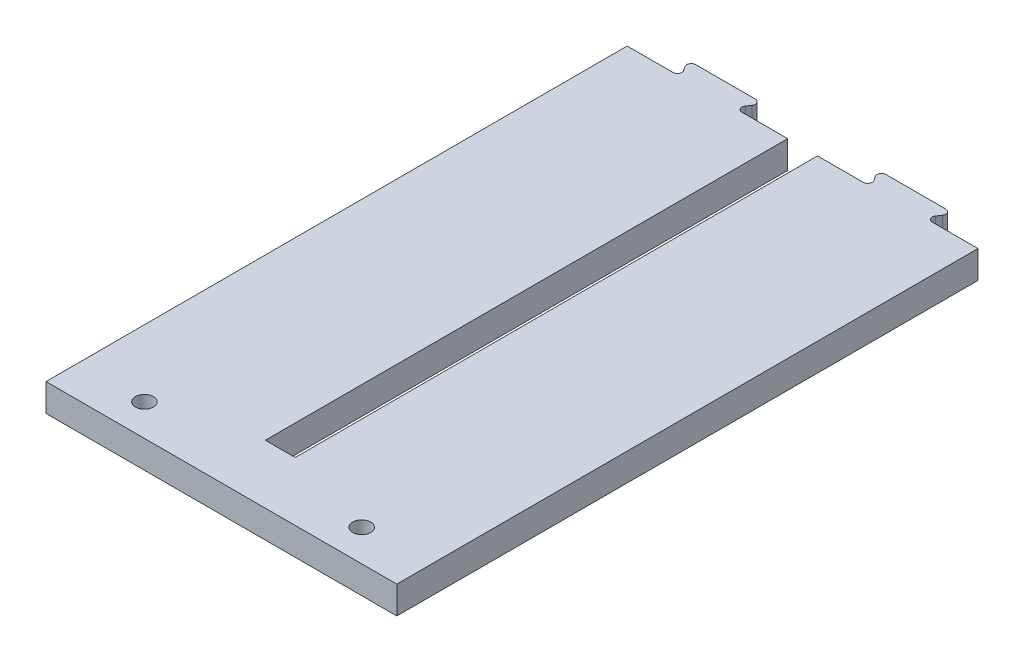
SolidWorks part; units mm, degrees
ref_plane "Front Plane" through (0, 0, 0) normal (0, 0, 1) x (1, 0, 0)
ref_plane "Top Plane" through (0, 0, 0) normal (0, 1, 0) x (1, 0, 0)
ref_plane "Right Plane" through (0, 0, 0) normal (1, 0, 0) x (0, 0, -1)
sketch "Sketch1" plane through (0, 0, 0) normal (0, 1, 0) x (1, 0, 0)
  line L1 (-19.375, 0) -> (19.375, 0)
  line L2 (-19.375, 0) -> (-19.375, 72.5)
  line L3 (-19.375, 72.5) -> (19.375, 72.5)
  line L4 (19.375, 0) -> (19.375, 72.5)
  point P5 (0, 0)
  dimension "D1" = 38.75
  dimension "D2" = 72.5
extrude "Boss-Extrude1" add sketch "Sketch1" along normal blind 3.05 contours L2 | L1 L4 L3 L2 | L4 region at (0, 0, -36.25)
sketch "Sketch4" plane through (0, 3.05, 0) normal (0, 1, 0) x (1, 0, 0)
  line L0 (-19.375, 72.5) -> (19.375, 72.5) construction
  line L2 (-19.375, 0) -> (19.375, 0) construction
  line L3 (1.65, 70.5) -> (-1.65, 70.5)
  line L4 (-1.65, 70.5) -> (-1.65, 69.5)
  line L5 (-1.65, 69.5) -> (1.65, 69.5)
  line L6 (1.65, 69.5) -> (1.65, 70.5)
  line L7 (0, 0) -> (0, 72.5) construction
  line L9 (1.65, 68.3) -> (-1.65, 68.3)
  line L10 (-1.65, 68.3) -> (-1.65, 6.5)
  line L11 (-1.65, 6.5) -> (1.65, 6.5)
  line L12 (1.65, 6.5) -> (1.65, 68.3)
  point P6 (0, 6.5)
  point P10 (0, 70.5)
  point P22 (0, 68.3)
  dimension "D1" = 2
  dimension "D2" = 1
  dimension "D3" = 1.2
  dimension "D4" = 3.3
  dimension "D7" = 6.5
extrude "Cut-Extrude1" cut sketch "Sketch4" against normal through all contours L5 L7 L3 L4 | L11 L7 L9 L10 | L7 L11 L12 L9 | L7 L5 L6 L3 | L6 L3 L4 L5 region at (0.825, 3.05, -70) region at (0.825, 3.05, -37.4) region at (-0.825, 3.05, -37.4) region at (-0.825, 3.05, -70)
sketch "Sketch7" plane through (0, 3.05, 0) normal (0, 1, 0) x (1, 0, 0)
  line L0 (0, 0) -> (-12, 0)
  line L1 (-19.375, 0) -> (19.375, 0) construction
  line L2 (-12, 0) -> (-12, 3.5)
  line L4 (0, 0) -> (0, 70) construction
  circle A0 centre (-12, 3.5) radius 1
  circle A2 centre (12, 3.5) radius 1
  dimension "D3" = 2
  dimension "D1" = 12
  dimension "D2" = 3.5
extrude "Cut-Extrude4" cut sketch "Sketch7" against normal through all contours A0 L2 | L2 A0 | A2 region at (-11.3129, 3.05, -2.8129)
sketch "Sketch8" plane through (0, 3.05, 0) normal (0, 1, 0) x (1, 0, 0)
  line L0 (19.375, 0) -> (19.375, 72.5) construction
  line L1 (-19.375, 72.5) -> (19.375, 72.5)
  line L2 (-19.375, 72.5) -> (-19.375, 64.2)
  line L3 (-19.375, 64.2) -> (19.375, 64.2)
  line L4 (19.375, 72.5) -> (19.375, 64.2)
  dimension "D1" = 8.3
extrude "Cut-Extrude5" cut sketch "Sketch8" against normal through all
sketch "Sketch9" plane through (0, 3.05, 0) normal (0, 1, 0) x (1, 0, 0)
  line L0 (-19.375, 64.2) -> (19.375, 64.2) construction
  line L1 (-19.375, 64.2) -> (-19.375, 66.2) construction
  line L2 (19.375, 64.2) -> (19.375, 66.2) construction
  line L3 (-19.375, 66.2) -> (19.375, 66.2) construction
  line L4 (-19.375, 64.2) -> (-13.375, 64.2)
  line L5 (-13.375, 64.2) -> (-14.7625, 66.2)
  line L6 (-14.7625, 66.2) -> (-6.2625, 66.2)
  line L7 (-6.2625, 66.2) -> (-7.65, 64.2)
  line L8 (-7.65, 64.2) -> (-1.65, 64.2)
  line L9 (1.65, 64.2) -> (7.65, 64.2)
  line L10 (7.65, 64.2) -> (6.2625, 66.2)
  line L11 (6.2625, 66.2) -> (14.7625, 66.2)
  line L12 (14.7625, 66.2) -> (13.375, 64.2)
  line L13 (13.375, 64.2) -> (19.375, 64.2)
  line L14 (-13.375, 64.2) -> (-7.65, 64.2)
  line L15 (7.65, 64.2) -> (13.375, 64.2)
  line L16 (-19.375, 66.2) -> (-14.7625, 66.2)
  line L17 (14.7625, 66.2) -> (19.375, 66.2)
  line M1 (-1.65, 64.2) -> (-19.375, 64.2)
  line M5 (19.375, 64.2) -> (1.65, 64.2)
  dimension "D1" = 2
  dimension "D3" = 8.5
  dimension "D4" = 6
extrude "Boss-Extrude3" add sketch "Sketch9" against normal blind 3.05 contours L7 L6 L5 M1 | L12 L11 L10 M5 region at (-10.5125, 3.05, -65.265) region at (10.5125, 3.05, -65.265)
fillet "Fillet2" radius 0.5 8 edges at (13.375, 1.525, -64.2) (-7.65, 1.525, -64.2) (14.7625, 1.525, -66.2) (7.65, 1.525, -64.2) (6.2625, 1.525, -66.2) (-6.2625, 1.525, -66.2) (-14.7625, 1.525, -66.2) (-13.375, 1.525, -64.2)
